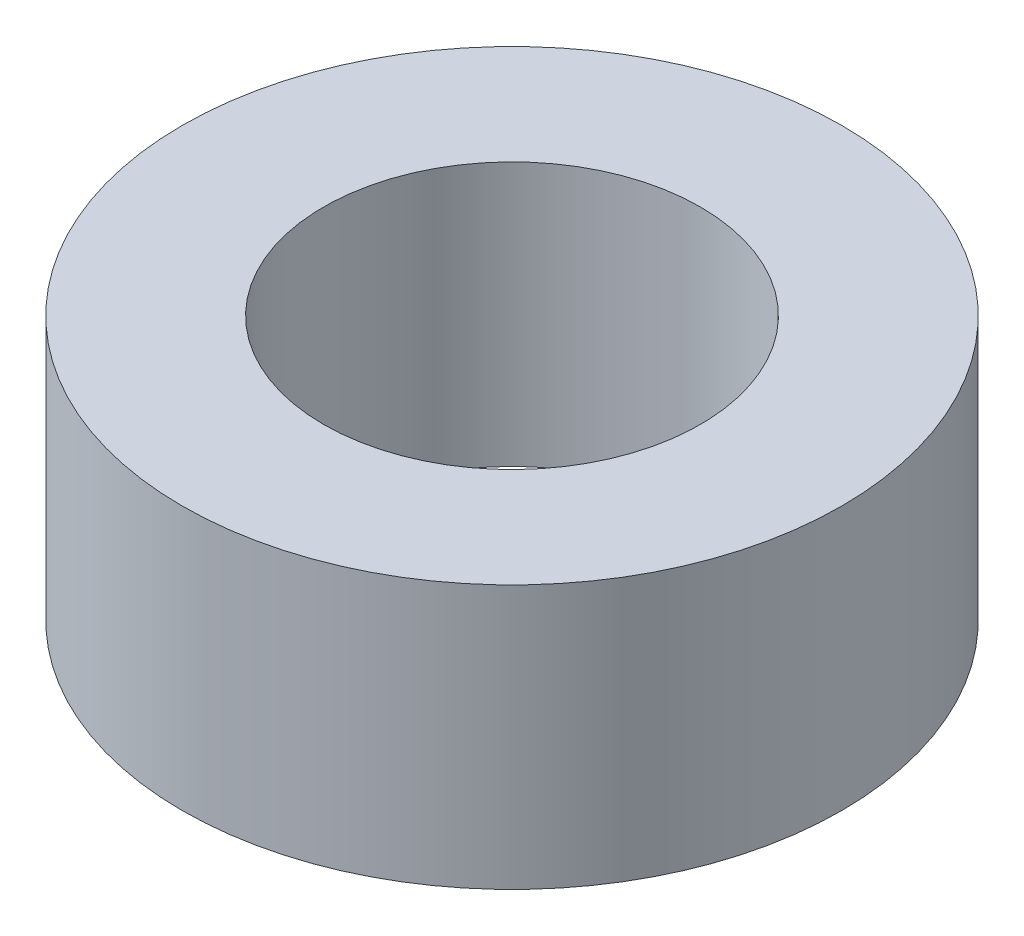
SolidWorks part; units mm, degrees
ref_plane "Front Plane" through (0, 0, 0) normal (0, 0, 1) x (1, 0, 0)
ref_plane "Top Plane" through (0, 0, 0) normal (0, 1, 0) x (1, 0, 0)
ref_plane "Right Plane" through (0, 0, 0) normal (1, 0, 0) x (0, 0, -1)
sketch "Sketch1" plane through (0, 0, 0) normal (0, 1, 0) x (1, 0, 0)
  circle A0 centre (0, 0) radius 17.5
  dimension "FLANGE_OD" = 35
extrude "Boss-Extrude1" add sketch "Sketch1" along normal blind 14
sketch "Sketch2" plane through (0, 0, 0) normal (0, 1, 0) x (1, 0, 0)
  circle A0 centre (0, 0) radius 10
  dimension "BORE_D" = 20
extrude "Cut-Extrude1" cut sketch "Sketch2" along normal through all
sketch "Sketch3" plane through (0, 14, 0) normal (0, 1, 0) x (1, 0, 0)
  circle A0 centre (0, 0) radius 7.2388 construction
  circle A1 centre (-7.2388, 0) radius 1.5
  dimension "BOLT_D" = 3
  dimension "BOLT_PCD" = 14.4777
extrude "Cut-Extrude2" cut sketch "Sketch3" against normal blind 9.0679 rebuild error yes
pattern_circular "CirPattern1" count 8 over 360 rebuild error yes
